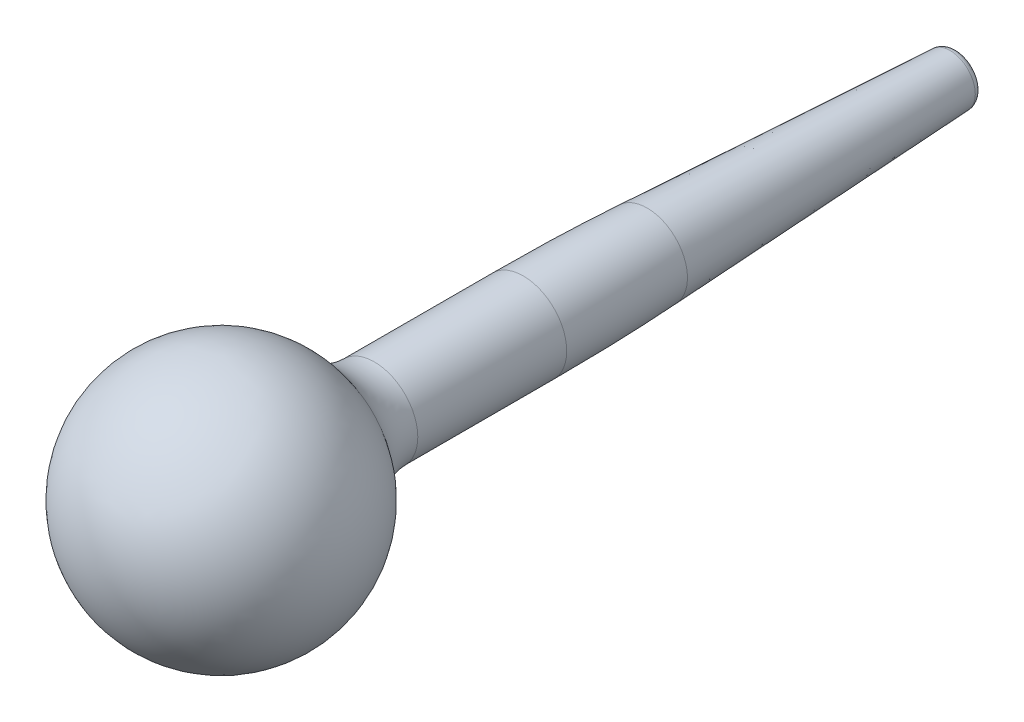
SolidWorks part; units mm, degrees
ref_plane "Front Plane" through (0, 0, 0) normal (0, 0, 1) x (1, 0, 0)
ref_plane "Top Plane" through (0, 0, 0) normal (0, 1, 0) x (1, 0, 0)
ref_plane "Right Plane" through (0, 0, 0) normal (1, 0, 0) x (0, 0, -1)
sketch "Sketch1" plane through (0, 0, 0) normal (0, 0, 1) x (1, 0, 0)
  circle A0 centre (0, 0) radius 4.445
  dimension "D1" = 8.89
extrude "Boss-Extrude1" add sketch "Sketch1" along normal blind 63.5
sketch "Sketch2" plane through (0, 0, 0) normal (1, 0, 0) x (0, 0, -1)
  line L0 (-63.5, 0) -> (-88.0967, 0)
  line L1 (-63.5, 4.445) -> (-63.5, -4.445) construction
  line L2 (-63.5, 4.445) -> (-63.5, 0)
  arc A1 (-88.0967, 0) -> (-63.5, 4.445) centre (-75.3967, 0) cw
  dimension "D1" = 12.7
revolve "Revolve1" add sketch "Sketch2" angle 360 about L0
sketch "Sketch3" plane through (0, 0, 0) normal (0, 0, -1) x (-1, 0, 0)
  line L1 (-0.7, 1.1) -> (0.7, 1.1)
  line L2 (-0.7, 1.1) -> (-0.7, -1.1)
  line L3 (-0.7, -1.1) -> (0.7, -1.1)
  line L4 (0.7, 1.1) -> (0.7, -1.1)
  point P2 (0.7, 0)
  point P5 (0, 1.1)
  dimension "D1" = 1.4
  dimension "D2" = 2.2
extrude "Cut-Extrude1" cut sketch "Sketch3" against normal blind 50.8
fillet "Fillet1" radius 6.35 1 edges at (4.445, 0, 63.5)
sketch "Sketch5" plane through (0, 0, 0) normal (0, 1, 0) x (1, 0, 0)
  line L0 (0, 0) -> (0, -38.1) construction
  line L1 (4.445, 0) -> (-4.445, 0) construction
  line L2 (0, -38.1) -> (-4.445, -38.1) construction
  line L3 (-4.445, 0) -> (-4.445, -59.7005) construction
  line L4 (-4.445, -38.1) -> (-2.54, 0)
  line L5 (-2.54, 0) -> (0, 0) construction
  line L6 (-4.445, -38.1) -> (-4.445, 0)
  line L7 (-4.445, 0) -> (-2.54, 0)
  dimension "D1" = 2.54
  dimension "D2" = 38.1
revolve "Cut-Revolve1" cut sketch "Sketch5" angle 360 about L0
fillet "Fillet2" radius 254 1 edges at (-4.445, 0, 38.1)
fillet "Fillet3" radius 0.762 1 edges at (-2.54, 0, 0)
